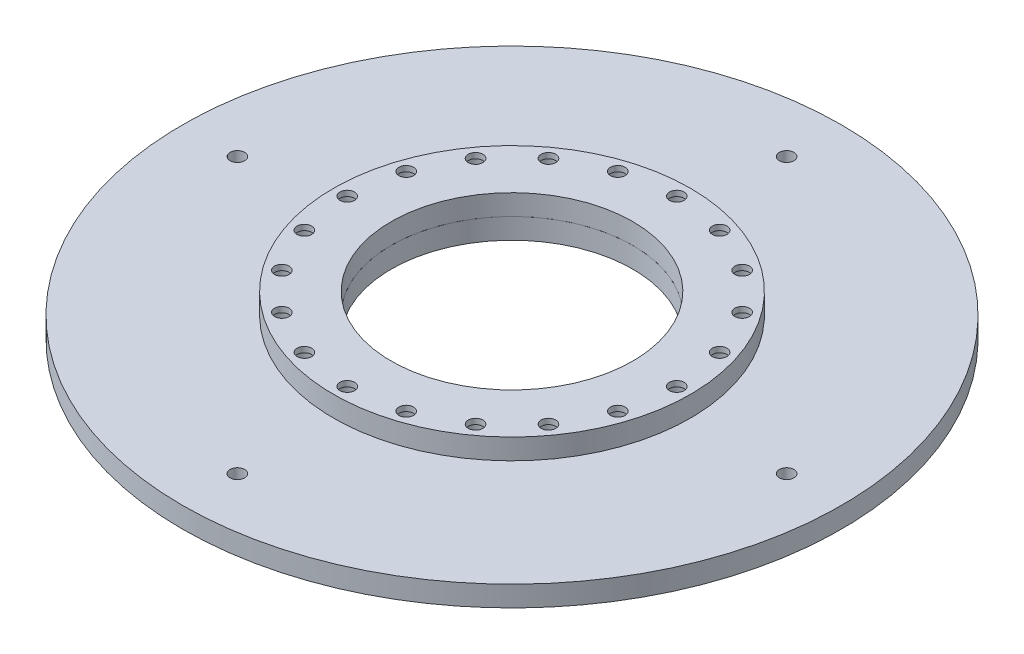
SolidWorks part; units mm, degrees
ref_plane "Front Plane" through (0, 0, 0) normal (0, 0, 1) x (1, 0, 0)
ref_plane "Top Plane" through (0, 0, 0) normal (0, 1, 0) x (1, 0, 0)
ref_plane "Right Plane" through (0, 0, 0) normal (1, 0, 0) x (0, 0, -1)
sketch "Sketch9" plane through (0, 0, 0) normal (0, 1, 0) x (1, 0, 0)
  circle A2 centre (0, 0) radius 82.55
  circle A4 centre (0, 0) radius 55.88
  circle A5 centre (0, 0) radius 76.2 construction
  point P6 (0, 76.2)
  point P34 (0, 0)
  dimension "Diameter_BackPlate" = 165.1
  dimension "Diameter_FuelOuterPlenum" = 111.76
  dimension "Diameter_BackPlate_BoltCircle" = 152.4
extrude "REF_BackPlate" add sketch "Sketch9" along normal blind 9.525 contours A2 A4 region at (-80.2151, 0, 0)
sketch "Sketch1" plane through (0, 0, 0) normal (0, 1, 0) x (1, 0, 0)
  line L1 (0, 82.55) -> (0, 81.788) construction
  line L2 (0, 81.788) -> (0, 76.2) construction
  line L3 (3.7419, 72.0498) -> (10.2656, 64.8143) construction
  line L5 (3.7419, 72.0498) -> (0, 76.2) construction
  line L6 (8.7416, 55.192) -> (10.2656, 64.8143) construction
  line L7 (0, 82.55) -> (0, 127) construction
  line L8 (39.2452, 120.7842) -> (25.5094, 78.5097) construction
  line L9 (8.7416, 55.192) -> (0, 0) construction
  line L12 (10.2656, 64.8143) -> (18.7059, 69.6798) construction
  line L13 (18.7059, 69.6798) -> (23.5471, 72.4705) construction
  circle A3 centre (0, 0) radius 152.4
  circle A8 centre (0, 0) radius 127 construction
  circle A14 centre (0, 76.2) radius 5.588 construction
  circle A15 centre (0, 0) radius 55.88 construction
  circle A17 centre (0, 0) radius 82.55 construction
  circle A18 centre (23.5471, 72.4705) radius 5.588 construction
  circle A19 centre (0, 0) radius 76.2 construction
  circle A20 centre (0, 0) radius 55.88
  point P2 (0, 127)
  point P5 (10.2656, 64.8143)
  dimension "Diameter_Takeout_BoltCircle" = 254
  dimension "Diameter_ThrustPlate" = 304.8
  dimension "D1" = 11.176
  dimension "D3" = 18
sketch "Sketch20" plane through (0, 0, 0) normal (0, -1, 0) x (-1, 0, 0)
  point P0 (0, 76.2)
hole_wizard "REF_CBORE_BackPlate" positions "Sketch20" profile "Sketch21" counterbore size "1/4" standard "ANSI Inch" end condition through all
sketch "Sketch21" plane through (0, 0, -76.2) normal (1, 0, 0) x (0, 0, -1)
  line L0 (0, 0) -> (0, 9.525)
  line L1 (0, 9.525) -> (3.3782, 9.525)
  line L3 (3.3782, 9.525) -> (3.3782, 6.985)
  line L4 (3.3782, 6.985) -> (5.588, 6.985)
  line L5 (5.588, 6.985) -> (5.588, 0)
  line L7 (5.588, 0) -> (0, 0)
  line L11 (0, -6.35) -> (0, 107.95) construction
  dimension "Thru Hole Dia." = 6.7564
  dimension "Thru Hole Depth" = 9.525
  dimension "C'Bore Dia." = 11.176
  dimension "C'Bore Depth" = 6.985
pattern_circular "REF_CBORE_BackPlate_Pattern" count 20 over 360 about axis through (0, 9.525, 0) along (0, -1, 0) of "REF_CBORE_BackPlate"
extrude "ThrustPlate_TC3" add sketch "Sketch1" against normal blind 9.525 separate body contours A3 region at (-148.0895, 0, 0)
sketch "Sketch11" plane through (0, 0, 0) normal (0, 1, 0) x (1, 0, 0)
  point P0 (0, 127)
hole_wizard "UNDEF_Clearance_ThrustPlate" positions "Sketch11" profile "Sketch12" hole size "1/4" standard "ANSI Inch" end condition through all
sketch "Sketch12" plane through (0, 0, -127) normal (1, 0, 0) x (0, 0, 1)
  line L0 (0, 0) -> (0, 9.525)
  line L1 (0, 9.525) -> (3.3782, 9.525)
  line L2 (3.3782, 9.525) -> (3.3782, 0)
  line L5 (3.3782, 0) -> (0, 0)
  line L11 (0, -6.35) -> (0, 107.95) construction
  dimension "Thru Hole Dia." = 6.7564
  dimension "Thru Hole Depth" = 9.525
pattern_circular "Clearance_ThrustPlate_Pattern" count 4 over 360 about axis through (0, -9.525, 0) along (0, 1, 0) of "UNDEF_Clearance_ThrustPlate" reverse direction yes
sketch "Sketch13" plane through (0, 0, 0) normal (0, 1, 0) x (1, 0, 0)
  point P0 (10.2656, 64.8143)
hole_wizard "UNDEF_Clearance_BackPlate" positions "Sketch13" profile "Sketch14" hole size "#12" standard "ANSI Inch" end condition through all
sketch "Sketch14" plane through (10.2656, 0, -64.8143) normal (1, 0, 0) x (0, 0, 1)
  line L0 (0, 0) -> (0, 9.525)
  line L1 (0, 9.525) -> (3.175, 9.525)
  line L2 (3.175, 9.525) -> (3.175, 0)
  line L5 (3.175, 0) -> (0, 0)
  line L11 (0, -6.35) -> (0, 107.95) construction
  dimension "Thru Hole Depth" = 9.525
  dimension "Thru Hole Dia." = 6.35
pattern_circular "UNDEF_Clearance_BackPlate_Pattern" count 10 over 360 about axis through (0, -9.525, 0) along (0, 1, 0) of "UNDEF_Clearance_BackPlate" reverse direction yes
sketch "Sketch24" plane through (0, 0, 0) normal (0, 1, 0) x (1, 0, 0)
  circle A0 centre (10.2656, 64.8143) radius 3.175 construction
  circle A1 centre (10.2656, 64.8143) radius 3.175
extrude "Cut-Extrude3" cut sketch "Sketch24" along normal blind 3.175
pattern_circular "CirPattern4" count 10 over 360 about axis through (0, -9.525, 0) along (0, 1, 0) of "Cut-Extrude3" reverse direction yes
equation "\"Diameter_BackPlate\"= 6.5"
equation "\"VAR_Diameter_BackPlate_BoltCircle\"= 6"
equation "\"VAR_Diameter_FuelOuterPlenum\"= 4.4"
equation "\"Diameter_BackPlate@Sketch9\"=\"Diameter_BackPlate\""
equation "\"Diameter_BackPlate_BoltCircle@Sketch9\"=\"VAR_Diameter_BackPlate_BoltCircle\""
equation "\"Diameter_FuelOuterPlenum@Sketch9\"=\"VAR_Diameter_FuelOuterPlenum\""
equation "\"Thickness_ThrustPlate\"= 0.375'undetermined"
equation "\"Diameter_ThrustPlate\"= 12'defined"
equation "\"Diameter_Takeout_BoltCicle\"= 10'defined"
equation "\"Diameter_Takeout_BoltCircle@Sketch1\"=\"Diameter_Takeout_BoltCicle\""
equation "\"Diameter_ThrustPlate@Sketch1\"=\"Diameter_ThrustPlate\""
equation "\"D1@ThrustPlate_TC3\"=\"Thickness_ThrustPlate\""
equation "\"VAR_Diameter_CBORE\"= 0.44'undetermined"
equation "\"VAR_Diameter_Clearance_ThrustPlate\"= 0.25'undetermined"
equation "\"D3@Sketch1\"=360/\"D1@REF_CBORE_BackPlate_Pattern\""
equation "\"D1@Sketch1\"=\"C'Bore Dia.@Sketch21\"''''''''''''''''''''''''''''"
equation "\"C'Bore Dia.@Sketch21\"=\"VAR_Diameter_CBORE\""
equation "\"Thru Hole Dia.@Sketch14\"=\"VAR_Diameter_Clearance_ThrustPlate\""
equation "\"NumberBolts_BackPlate\"= 20"
equation "\"NumberBolts_Takeout\"= 4'defined"
equation "\"D1@Clearance_ThrustPlate_Pattern\"=\"NumberBolts_Takeout\""
equation "\"D1@REF_CBORE_BackPlate_Pattern\"=\"NumberBolts_BackPlate\""
equation "\"D1@UNDEF_Clearance_BackPlate_Pattern\"=\"NumberBolts_BackPlate\"/2"
equation "\"D1@CirPattern4\"=\"D1@UNDEF_Clearance_BackPlate_Pattern\""
